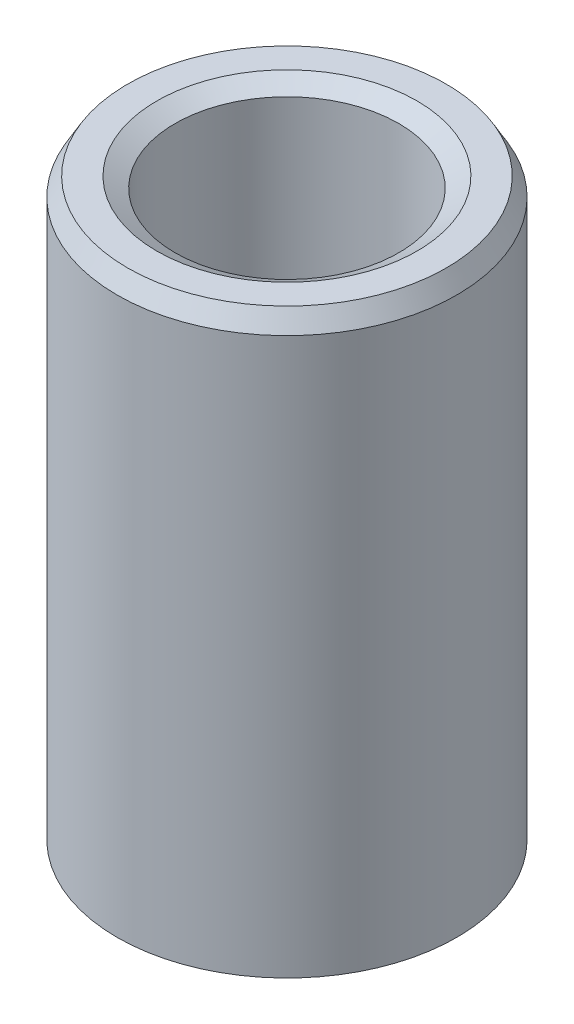
SolidWorks part; units mm, degrees
ref_plane "Front Plane" through (0, 0, 0) normal (0, 0, 1) x (1, 0, 0)
ref_plane "Top Plane" through (0, 0, 0) normal (0, 1, 0) x (1, 0, 0)
ref_plane "Right Plane" through (0, 0, 0) normal (1, 0, 0) x (0, 0, -1)
sketch "Sketch1" plane through (0, 0, 0) normal (0, 1, 0) x (1, 0, 0)
  circle A0 centre (0, 0) radius 25
  dimension "SLEEVE_OD" = 50
extrude "Boss-Extrude1" add sketch "Sketch1" along normal blind 86.1242
sketch "Sketch2" plane through (0, 0, 0) normal (0, 1, 0) x (1, 0, 0)
  circle A0 centre (0, 0) radius 16.4784
  dimension "BORE_D" = 32.9568
extrude "Cut-Extrude1" cut sketch "Sketch2" along normal through all
chamfer "Chamfer1" distance 2.6764 angle 30 4 edges at (0, 86.1242, 16.4784) (0, 0, 16.4784) (0, 0, 25) (0, 86.1242, 25) first distance on face at (0, 86.1242, 16.4784) first distance on face at (0, 0, 16.4784) first distance on face at (0, 86.1242, 25)
